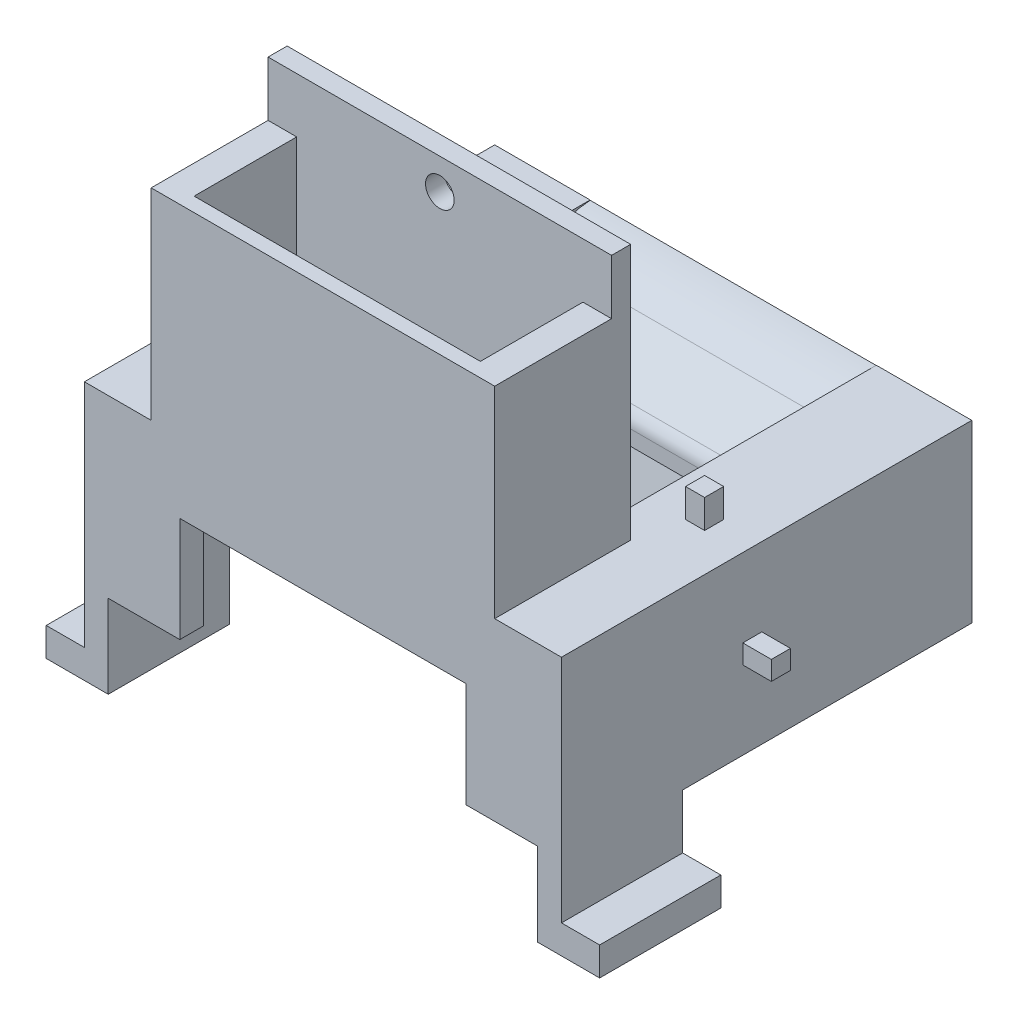
SolidWorks part; units mm, degrees
ref_plane "Front Plane" through (0, 0, 0) normal (0, 0, 1) x (1, 0, 0)
ref_plane "Top Plane" through (0, 0, 0) normal (0, 1, 0) x (1, 0, 0)
ref_plane "Right Plane" through (0, 0, 0) normal (1, 0, 0) x (0, 0, -1)
sketch "Sketch1" plane through (0, 0, 0) normal (0, 0, 1) x (1, 0, 0)
  line L1 (-25, 9.2) -> (25, 9.2)
  line L2 (-25, 9.2) -> (-25, -9.2)
  line L3 (-25, -9.2) -> (25, -9.2)
  line L4 (25, 9.2) -> (25, -9.2)
  line L5 (-25, 9.2) -> (25, -9.2) construction
  line L6 (-25, -9.2) -> (25, 9.2) construction
  point P0 (0, 0)
  dimension "D1" = 50
  dimension "D2" = 18.4
extrude "Boss-Extrude1" add sketch "Sketch1" along normal blind 43
sketch "Sketch2" plane through (0, -9.2, 0) normal (0, -1, 0) x (-1, 0, 0)
  line L0 (-25, -43) -> (-25, 0) construction
  line L1 (-22.5, -14.5) -> (-15, -14.5)
  line L2 (-22.5, -14.5) -> (-22.5, -9.5)
  line L3 (-22.5, -9.5) -> (-15, -9.5)
  line L4 (-15, -14.5) -> (-15, -9.5)
  line L5 (25, 0) -> (-25, 0) construction
  line L6 (22.5, -14.5) -> (15, -14.5)
  line L7 (22.5, -14.5) -> (22.5, -9.5)
  line L8 (22.5, -9.5) -> (15, -9.5)
  line L9 (15, -14.5) -> (15, -9.5)
  line L10 (-22.5, -12) -> (-25, -12) construction
  line L11 (15, -12.9) -> (-15, -12.9)
  line L12 (15, -12.9) -> (15, -11.1)
  line L13 (15, -11.1) -> (-15, -11.1)
  line L14 (-15, -12.9) -> (-15, -11.1)
  line L15 (22.5, -12) -> (25, -12) construction
  line L19 (25, -43) -> (25, 0) construction
  point P12 (15, -12)
  point P13 (-15, -12)
  point P15 (15, -12)
  line M14 (-25, 0) -> (-25, -43)
  line M16 (25, -43) -> (25, 0)
  dimension "D1" = 5
  dimension "D2" = 7.5
  dimension "D3" = 1.8
  dimension "D4" = 2.5
  dimension "IRdist" = 12
extrude "Cut-Extrude1" cut sketch "Sketch2" against normal blind 15.6 contours L9 L6 L8 M16 | L9 L13 L4 L11 | L1 L4 L3 M14 region at (18.75, -9.2, 12) region at (0, -9.2, 12) region at (-18.75, -9.2, 12)
sketch "Sketch3" plane through (0, 0, 0) normal (1, 0, 0) x (0, 0, -1)
  line L0 (-2.5, -9.2) -> (-2.5, 6.2)
  line L1 (-43, -9.2) -> (0, -9.2) construction
  line L2 (-2.5, 6.2) -> (-11.8253, -1.1447)
  line L3 (-11.8253, -1.1447) -> (-40.5, 6.2)
  line L4 (-40.5, 6.2) -> (-40.5, -9.2)
  line L5 (-40.5, -9.2) -> (-2.5, -9.2)
  line L6 (-43, 9.2) -> (0, 9.2) construction
  line L7 (-43, 9.2) -> (0, 9.2) construction
  line L8 (-43, 9.2) -> (-43, -9.2) construction
  line L9 (-2.7315, 9.2) -> (-12, 1.9)
  line L10 (-12, 1.9) -> (-40.5, 9.2)
  line L11 (-40.5, 9.2) -> (-2.7315, 9.2)
  line L12 (-14.5, 6.4) -> (-9.5, 6.4) construction
  line L13 (0, 9.2) -> (0, -9.2) construction
  line L14 (-21.6873, 4.3813) -> (-12, 1.6)
  line L15 (-12, 1.6) -> (-12, 1.9)
  dimension "D1" = 2.5
  dimension "D3" = 2.5
  dimension "D4" = 4.5
  dimension "D2" = 3
  dimension "D5" = 2.5
  dimension "D6" = 12
  dimension "D7" = 0.3
  dimension "D8" = 10
extrude "Cut-Extrude2" cut sketch "Sketch3" against normal up to vertex (22.5 mm away) contours L4 L5 L0 L2 L3 region at (0, -3.1445, 22.5098) up to point (-22.5, -9.2, 14.5)
mirror "Mirror3" about plane through (0, 0, 0) normal (1, 0, 0) of "Cut-Extrude2"
extrude "Cut-Extrude3" cut sketch "Sketch3<3>" against normal up to vertex (15 mm away) contours L11 L10 L9 | L14 L15 L10 region at (0, 6.7667, 18.4105) region at (0, 2.6271, 15.2291) up to point (-15, -0.8695, 12.9)
sketch "Sketch3<3>" plane through (0, 0, 0) normal (1, 0, 0) x (0, 0, -1) same geometry as "Sketch3"
mirror "Mirror4" about plane through (0, 0, 0) normal (1, 0, 0) of "Cut-Extrude3"
sketch "Sketch12" plane through (22.5, 0, 0) normal (-1, 0, 0) x (0, 0, 1)
  line L0 (9.5, 6.4) -> (9.5, 0.6867)
  line L1 (9.5, 0.6867) -> (9.625, 6.4)
  line L3 (9.625, 6.4) -> (9.5, 6.4)
  line L4 (14.5, 6.4) -> (14.5, 0.6867)
  line L5 (14.5, 0.6867) -> (14.375, 6.4)
  line L6 (14.375, 6.4) -> (14.5, 6.4)
  dimension "D1" = 4.75
extrude "Boss-Extrude3" add sketch "Sketch12" along normal up to surface (7.5 mm away) up to face at (15, 5.9669, 16.1312)
extrude "Boss-Extrude4" add sketch "Sketch12<2>" against normal up to surface (-37.5 mm away) from surface up to face at (-15, 1.6478, 10.3) starting at face at (-22.5, 0.8784, 16.75)
sketch "Sketch12<2>" plane through (22.5, 0, 0) normal (-1, 0, 0) x (0, 0, 1) same geometry as "Sketch12"
sketch "Sketch17" plane through (-15, 0, 0) normal (1, 0, 0) x (0, 0, -1)
  line L0 (-43, 9.2) -> (-43, 10.7)
  line L1 (-43, 10.7) -> (-21.6873, 4.3813)
  line L2 (-21.6873, 4.3813) -> (-40.5, 9.2)
  line L3 (-40.5, 9.2) -> (-43, 9.2)
  dimension "D1" = 1.5
extrude "Boss-Extrude7" add sketch "Sketch17" along normal up to surface (30 mm away) up to face at (15, 5.9577, 16.136)
sketch "Sketch18" plane through (15, 0, 0) normal (1, 0, 0) x (0, 0, -1)
  line L0 (-43, 10.7) -> (-43, 9.2)
  line L1 (-43, 9.2) -> (-37.9406, 9.2)
  line L2 (-43, 9.2) -> (-37.9406, 9.2) construction
  line L4 (-37.9406, 9.2) -> (-43, 10.7)
  line L5 (-43, 10.7) -> (-37.9406, 9.2) construction
extrude "Mtrl Rmv" cut sketch "Sketch18" against normal through all
ref_plane "Plane4" through (0, 0, 30.75) normal (0, 0, 1) x (1, 0, 0)
sketch "Sketch23" plane through (15, 0, 0) normal (-1, 0, 0) x (0, 0, 1)
  line L0 (21.6873, 4.3813) -> (14.4645, 2.3076) construction
  line L1 (30.75, -26.9374) -> (30.75, 26.9374) construction
  point P0 (30.75, 6.9833)
sketch "Sketch22" plane through (0, 0, 30.75) normal (0, 0, 1) x (1, 0, 0)
  line L0 (18, 36.05) -> (18, 10.9833)
  line L1 (18, 10.9833) -> (18, 9.2)
  line L2 (18, 36.05) -> (-18, 36.05)
  line L3 (18, 10.9833) -> (-18, 10.9833)
  line L4 (-18, 10.9833) -> (-18, 36.05)
  line L5 (15, 10.9833) -> (15, 6.9833) construction
  line L6 (15, 6.4) -> (15, 2.3076) construction
  line L7 (25, 9.2) -> (-25, 9.2) construction
  line L8 (15, 10.9833) -> (15, 9.2)
  line L9 (0, 10.9833) -> (0, 0) construction
  line L10 (18, 9.2) -> (15, 9.2)
  line L11 (-25, -9.2) -> (25, -9.2) construction
  line L12 (-18, 10.9833) -> (-18, 9.2)
  line L13 (-18, 9.2) -> (-15, 9.2)
  line L14 (-15, 9.2) -> (-15, 10.9833)
  dimension "D1" = 4
  dimension "D2" = 3
  dimension "D3" = 45.25
extrude "Boss-Extrude8" add sketch "Sketch22" against normal blind 2 contours L4 L3 L0 L2 | L10 L1 L3 L8 | L13 L14 L3 L12 region at (0, 23.5166, 30.75) region at (16.5, 10.0916, 30.75) region at (-16.5, 10.0916, 30.75)
sketch "Sketch25" plane through (18, 0, 0) normal (1, 0, 0) x (0, 0, -1)
  line L0 (-43, -9.2) -> (0, -9.2) construction
  line L1 (-43, 9.2) -> (-41.5, 9.2)
  line L2 (-43, 9.2) -> (-43, 30.3)
  line L3 (-43, 30.3) -> (-41.5, 30.3)
  line L4 (-41.5, 9.2) -> (-41.5, 30.3)
  line L5 (-35.6253, 18.5428) -> (-41.5, 23.3)
  line L6 (-35.6253, 18.5428) -> (-41.5, 18.5428)
  line L7 (-30.75, 18.5428) -> (-35.2377, 12.1487)
  line L8 (-30.75, 36.05) -> (-30.75, 9.2) construction
  line L9 (-35.2377, 12.1487) -> (-30.75, 12.1487)
  line L10 (-41.5, 10.2553) -> (-37.9406, 9.2)
  line L11 (-43, 9.2) -> (0, 9.2) construction
  line L12 (-21.6873, 4.3813) -> (-37.9406, 9.2) construction
  line L13 (-37.9406, 9.2) -> (-41.5, 9.2)
  line L14 (-35.2377, 12.1487) -> (-37.9406, 9.2) construction
  line L15 (-35.6253, 18.5428) -> (-32.5168, 16.0255) construction
  line L16 (-35.2377, 12.1487) -> (-35.2377, 8.3987) construction
  line L17 (-35.2377, 12.1487) -> (-30.75, 10.9833)
  line L18 (-30.75, 10.9833) -> (-30.75, 6.9833) construction
  line L19 (-30.75, 36.05) -> (-30.75, 9.2) construction
  line L22 (-21.6873, 4.3813) -> (-14.4645, 2.3076) construction
  line L23 (-30.75, 10.9833) -> (-30.75, 12.1487)
  line M36 (-30.75, 36.05) -> (-30.75, 9.2)
  dimension "D1" = 1.5
  dimension "D2" = 39.5
  dimension "D3" = 3.75
  dimension "D4" = 51
  dimension "D5" = 7
  dimension "D6" = 4
  dimension "D7" = 4
  dimension "D8" = 4
extrude "Boss-Extrude9" add sketch "Sketch25" against normal up to surface (36 mm away) contours L1 L4 L3 L2 | L6 L5 L4 | L13 L10 L4 | L9 L17 M36 | L7 L9 M36 region at (18, 19.75, 42.25) region at (18, 9.5518, 40.3135) region at (18, 20.1285, 39.5418) region at (18, 14.28, 32.2459) region at (18, 11.7602, 32.2459) up to face at (-18, 22.625, 29.75)
sketch "Sketch27" plane through (0, 0, 43) normal (0, 0, 1) x (1, 0, 0)
  line L0 (-18, 30.3) -> (18, 30.3) construction
  line L1 (-18, 9.2) -> (-15, 9.2)
  line L2 (-18, 9.2) -> (-18, 30.3)
  line L3 (-18, 30.3) -> (-15, 30.3)
  line L4 (-15, 9.2) -> (-15, 30.3)
  line L5 (25, 9.2) -> (18, 9.2) construction
  line L6 (18, 9.2) -> (15, 9.2)
  line L7 (18, 9.2) -> (18, 30.3)
  line L8 (18, 30.3) -> (15, 30.3)
  line L9 (15, 9.2) -> (15, 30.3)
extrude "Boss-Extrude10" add sketch "Sketch27" against normal up to surface (14.25 mm away) up to face at (0, 16.3583, 28.75)
sketch "Sketch28" plane through (0, 0, 28.75) normal (0, 0, -1) x (-1, 0, 0)
  line L0 (18, 30.3) -> (-18, 30.3) construction
  line L1 (-18, 36.05) -> (18, 36.05) construction
  circle A0 centre (0, 32.8) radius 1.5
  point P7 (0, 36.05)
  dimension "D1" = 3
  dimension "D2" = 2.5
extrude "Cut-Extrude4" cut sketch "Sketch28" against normal through all
sketch "Sketch4" plane through (0, 0, 43) normal (0, 0, 1) x (1, 0, 0)
  line L0 (-25, -9.2) -> (25, -9.2) construction
  line L1 (-15, -9.2) -> (15, -9.2)
  line L2 (-15, -9.2) -> (-15, 1.8)
  line L3 (-15, 1.8) -> (15, 1.8)
  line L4 (15, -9.2) -> (15, 1.8)
  point P6 (0, 1.8)
  dimension "D1" = 30
  dimension "D2" = 11
extrude "Wire Hole" cut sketch "Sketch4" against normal up to surface (2.5 mm away) up to face at (0, -1.5, 40.5)
sketch "Sketch13" plane through (0, 0, 0) normal (0, 0, -1) x (-1, 0, 0)
  line L0 (-13, 0) -> (13, 0) construction
  line L1 (-15, 1) -> (-13, 1)
  line L2 (-15, 1) -> (-15, -1)
  line L3 (-15, -1) -> (-13, -1)
  line L4 (-13, 1) -> (-13, -1)
  line L5 (13, 1) -> (15, 1)
  line L6 (13, 1) -> (13, -1)
  line L7 (13, -1) -> (15, -1)
  line L8 (15, 1) -> (15, -1)
  point P16 (0, 0)
  dimension "D1" = 2
  dimension "D2" = 7.5
extrude "Front Shield Pegs" add sketch "Sketch13" along normal blind 2.9972
sketch "Sketch14" plane through (0, 9.2, 0) normal (0, 1, 0) x (1, 0, 0)
  line L0 (19, -23) -> (-19, -23) construction
  line L1 (21, -22) -> (19, -22)
  line L2 (21, -22) -> (21, -24)
  line L3 (21, -24) -> (19, -24)
  line L4 (19, -22) -> (19, -24)
  line L5 (-19, -22) -> (-21, -22)
  line L6 (-19, -22) -> (-19, -24)
  line L7 (-19, -24) -> (-21, -24)
  line L8 (-21, -22) -> (-21, -24)
  line L10 (25, -43) -> (18, -43) construction
  point P8 (0, -23)
  point P12 (21, -23)
  dimension "D1" = 2
  dimension "D2" = 20
  dimension "D3" = 4
extrude "Top Shield Pegs" add sketch "Sketch14" along normal blind 2.9972
fillet "Fillet9" radius 10 1 edges at (0, 9.2, 2.7315)
fillet "Fillet10" radius 2 1 edges at (0, 2.6089, 11.1)
ref_plane "Plane3" through (0, 0, 19) normal (0, 0, 1) x (1, 0, 0)
sketch "Sketch19" plane through (0, 0, 19) normal (0, 0, 1) x (1, 0, 0)
  line L0 (22.5, -9.2) -> (22.5, -17.915)
  line L1 (22.5, -17.915) -> (29, -17.915)
  line L2 (29, -17.915) -> (29, -14.915)
  line L3 (29, -14.915) -> (25, -14.915)
  line L4 (25, -14.915) -> (25, -9.2)
  line L5 (25, -9.2) -> (22.5, -9.2)
  line L6 (-22.5, -9.2) -> (-22.5, -17.915)
  line L7 (-22.5, -17.915) -> (-29, -17.915)
  line L8 (-29, -17.915) -> (-29, -14.915)
  line L9 (-29, -14.915) -> (-25, -14.915)
  line L10 (-25, -14.915) -> (-25, -9.2)
  line L11 (-25, -9.2) -> (-22.5, -9.2)
  dimension "D1" = 4
  dimension "D2" = 5.715
  dimension "D3" = 3
extrude "Legs" add sketch "Sketch19" against normal blind 12.7 from surface starting at face at (0, 5.35, 43)
sketch "Sketch29" plane through (-25, 0, 0) normal (-1, 0, 0) x (0, 0, 1)
  line L0 (23, 1) -> (23, 12.1972) construction
  line L1 (22, 1) -> (24, 1)
  line L2 (22, 1) -> (22, -1)
  line L3 (22, -1) -> (24, -1)
  line L4 (24, 1) -> (24, -1)
  line L5 (22, 12.1972) -> (24, 12.1972) construction
  line L7 (22, 12.1972) -> (22, 9.2) construction
  line L8 (22, 0) -> (-2.9972, 0) construction
  line L9 (-2.9972, -1) -> (-2.9972, 1) construction
extrude "Side Shield Pegs1" add sketch "Sketch29" along normal blind 2.9972
extrude "Side Shield Pegs2" add sketch "Sketch29<2>" against normal blind 2.9972 from surface starting at face at (25, -4.9717, 24.4333)
sketch "Sketch29<2>" plane through (-25, 0, 0) normal (-1, 0, 0) x (0, 0, 1) same geometry as "Sketch29"
fillet "Fillet3" [suppressed] radius 3
fillet "Fillet5" [suppressed] radius 3
fillet "Fillet6" [suppressed] radius 3 tangent propagation no
sketch "Sketch5" [suppressed] plane through (0, 0, 0) normal (1, 0, 0) x (0, 0, -1)
  line L0 (-40, 3.5229) -> (-61, 15.1419)
  line L1 (-45.2, 16.8) -> (-45.2, 18.347)
  line L2 (-61, 15.1419) -> (-61, 22.3)
  line L3 (-61, 22.3) -> (-45.2, 22.3)
  line L5 (-45.2, 16.8) -> (-40, 13.9229)
  line L6 (-40, 13.9229) -> (-40, 3.5229)
  line L7 (-40, 6.2) -> (-40, -9.2) construction
  line L8 (-45.2, 18.347) -> (-45.2, 22.3)
  line L10 (0, 9.2) -> (-40, 9.2) construction
  line L11 (-45.2, 22.3) -> (-61, 22.3)
  line L12 (-45.2, 22.3) -> (-45.2, 30.675)
  line L13 (-45.2, 30.675) -> (-61, 30.675)
  line L14 (-61, 22.3) -> (-61, 30.675)
  line L19 (-40, 13.9229) -> (-35.4398, 11.3998)
  line L20 (-35.4398, 11.3998) -> (-35.4398, 9.2)
  line L22 (-35.4398, 9.2) -> (-40, 9.2)
  dimension "D1" = 24
  dimension "D2" = 21
  dimension "D3" = 13.1
  dimension "D4" = 5.2
  dimension "D5" = 5.5
  dimension "D6" = 10.4
  dimension "D7" = 8.375
extrude "Ramp Extrude" [suppressed] add sketch "Sketch5" along normal mid plane 15
ref_plane "Plane2" [suppressed] through (0, 7.2819, -2.3953) normal (0, 0.9499, -0.3125) x (1, 0, 0)
sketch "Sketch7" [suppressed] plane through (0, 0, 0) normal (1, 0, 0) x (0, 0, -1)
  line L1 (-61, 15.1419) -> (-61, 30.675) construction
  line L2 (-60, 19.3) -> (-60, 22.3)
  line L3 (-60, 22.3) -> (-45.2, 22.3)
  line L4 (-60, 22.3) -> (-45.2, 22.3)
  line L5 (-45.2, 22.3) -> (-45.2, 16.8)
  line L8 (-60, 22.3) -> (-60, 30.675)
  line L9 (-35.4398, 11.3998) -> (-35.4398, 9.2)
  line L10 (-45.2, 27.675) -> (-60, 27.675) construction
  line L11 (-60, 30.675) -> (-45.2, 30.675)
  line L12 (-45.2, 22.3) -> (-45.2, 30.675)
  line L13 (-45.2, 30.675) -> (-61, 30.675) construction
  line L14 (-45.2, 16.8) -> (-45.2, 30.675) construction
  line L17 (-45.2, 16.8) -> (-35.4398, 11.3998)
  line L21 (-35.4398, 9.2) -> (-54.0763, 18.2247)
  arc A0 (-60, 27.675) -> (-54.0763, 18.2247) centre (-49.5, 27.675) ccw
  dimension "D5" = 10.5
  dimension "D1" = 1
  dimension "D2" = 3
  dimension "D3" = 5.5
  dimension "D4" = 3
extrude "Ramp Shell Cut" [suppressed] cut sketch "Sketch7" against normal mid plane 13
sketch "Sketch8" [suppressed] plane through (-7.5, 0, 0) normal (-1, 0, 0) x (0, 0, 1)
  line L0 (45.2, 23.7375) -> (49.15, 30.675)
  line L1 (45.2, 16.8) -> (45.2, 30.675) construction
  line L2 (45.2, 30.675) -> (61, 30.675) construction
  line L3 (49.15, 30.675) -> (45.2, 30.675)
  line L4 (45.2, 30.675) -> (45.2, 23.7375)
  line L5 (45.2, 23.7375) -> (53.1, 23.7375) construction
  point P9 (53.1, 30.675)
  point P12 (49.15, 23.7375)
extrude "Ramp Corner Cuts" [suppressed] cut sketch "Sketch8" against normal through all
equation "\"bottomThickness\"= .220in"
equation "\"wallThickness\"= .118in"
equation "\"D1@Front Shield Pegs\" = \"wallThickness\""
equation "\"D1@Top Shield Pegs\" = \"wallThickness\""
equation "\"IRdist\"=12"
equation "\"IRdist@Sketch2\"=\"IRdist\""
equation "\"D6@Sketch3\"=\"IRdist\""
equation "\"D1@Side Shield Pegs1\" = \"wallThickness\""
equation "\"D1@Side Shield Pegs2\" = \"wallThickness\""
equation "\"D2@Sketch19\"=\"bottomThickness\"+.005in"
